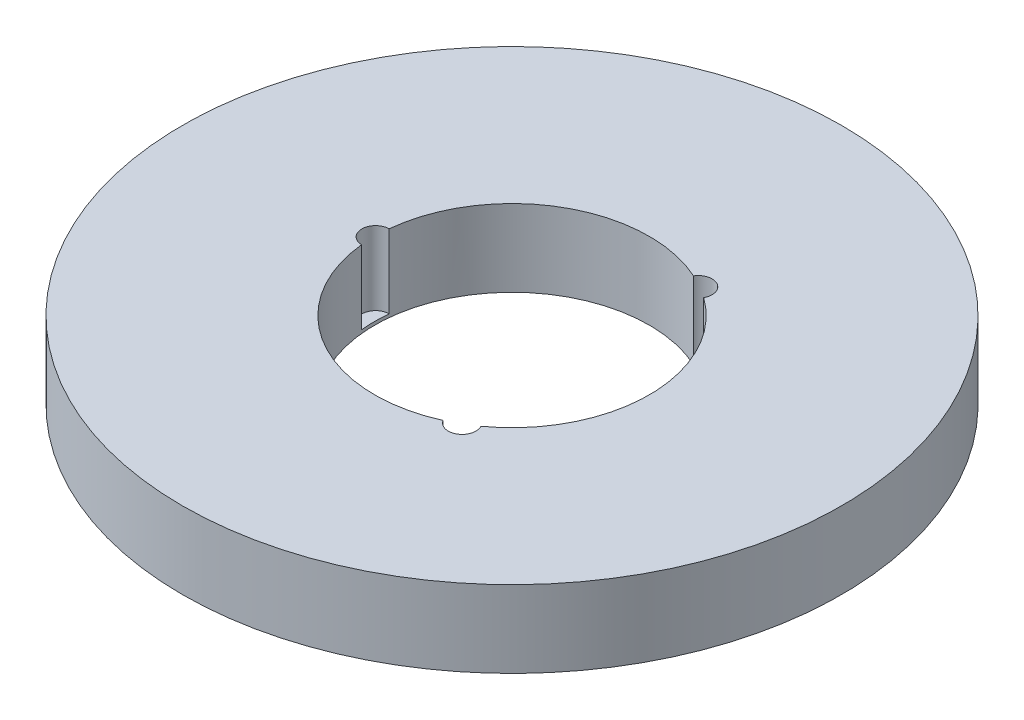
SolidWorks part; units mm, degrees
ref_plane "Front Plane" through (0, 0, 0) normal (0, 0, 1) x (1, 0, 0)
ref_plane "Top Plane" through (0, 0, 0) normal (0, 1, 0) x (1, 0, 0)
ref_plane "Right Plane" through (0, 0, 0) normal (1, 0, 0) x (0, 0, -1)
sketch "Sketch1" plane through (0, 0, 0) normal (0, 1, 0) x (1, 0, 0)
  circle A0 centre (0, 0) radius 60
  dimension "FLANGE_OD" = 120
extrude "Boss-Extrude1" add sketch "Sketch1" along normal blind 14
sketch "Sketch2" plane through (0, 0, 0) normal (0, 1, 0) x (1, 0, 0)
  circle A0 centre (0, 0) radius 25
  dimension "BORE_D" = 50
extrude "Cut-Extrude1" cut sketch "Sketch2" along normal through all
sketch "Sketch3" plane through (0, 14, 0) normal (0, 1, 0) x (1, 0, 0)
  circle A0 centre (0, 0) radius 24.8236 construction
  circle A1 centre (-24.8236, 0) radius 2.5156
  dimension "BOLT_D" = 5.0311
  dimension "BOLT_PCD" = 49.6473
extrude "Cut-Extrude2" cut sketch "Sketch3" against normal blind 13.4073
pattern_circular "CirPattern1" count 3 over 360 about axis through (0, 0, 0) along (0, 1, 0) of "Cut-Extrude2"
